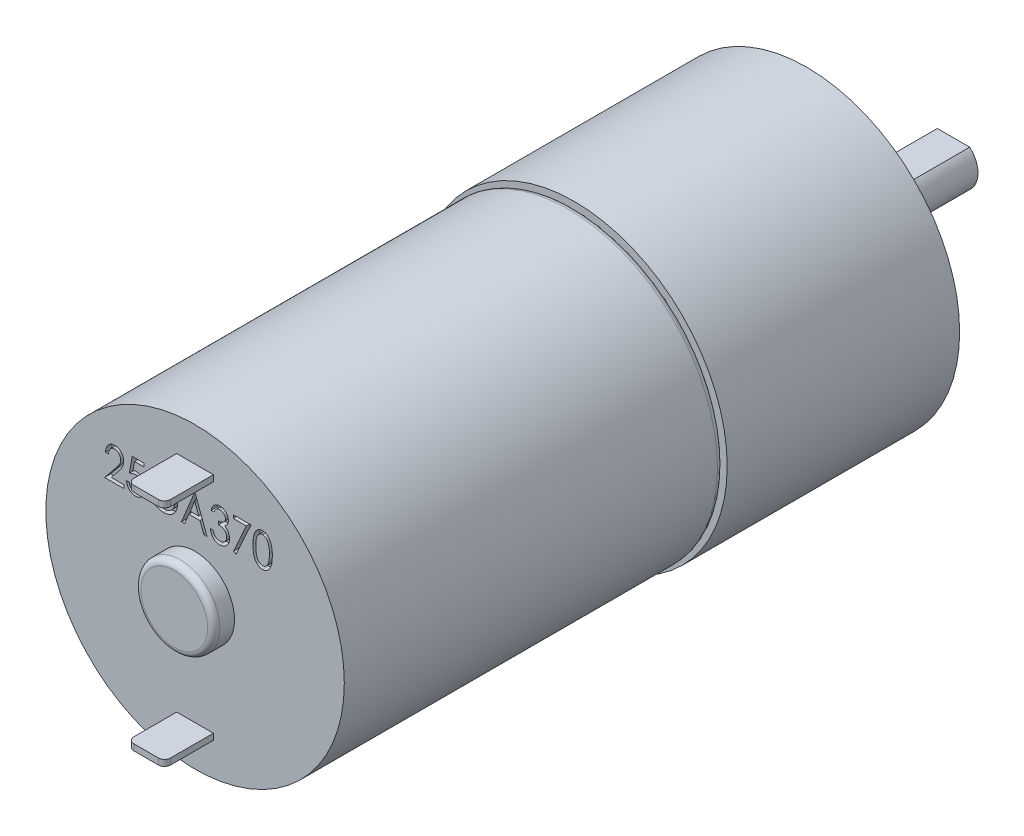
SolidWorks part; units mm, degrees
ref_plane "Front Plane" through (0, 0, 0) normal (0, 0, 1) x (1, 0, 0)
ref_plane "Top Plane" through (0, 0, 0) normal (0, 1, 0) x (1, 0, 0)
ref_plane "Right Plane" through (0, 0, 0) normal (1, 0, 0) x (0, 0, -1)
sketch "Sketch1" plane through (0, 0, 0) normal (0, 0, 1) x (1, 0, 0)
  circle A0 centre (0, 0) radius 12.2
  dimension "D1" = 24.4
extrude "Boss-Extrude1" add sketch "Sketch1" along normal blind 31
fillet "Fillet1" radius 0.5 1 edges at (12.2, 0, 0)
sketch "Sketch2" plane through (0, 0, 0) normal (0, 0, -1) x (-1, 0, 0)
  circle A0 centre (0, 0) radius 12.5
  dimension "D1" = 25
extrude "Boss-Extrude2" add sketch "Sketch2" along normal blind 19
sketch "Sketch4" plane through (0, 0, -19) normal (0, 0, -1) x (-1, 0, 0)
  circle A0 centre (0, 0) radius 3.5
  circle A1 centre (0, 0) radius 2.5
  dimension "D1" = 7
  dimension "D2" = 5
extrude "Boss-Extrude3" add sketch "Sketch4" along normal blind 2.5 contours A0
sketch "Sketch6" plane through (0, 0, -21.5) normal (0, 0, -1) x (-1, 0, 0)
  circle A0 centre (0, 0) radius 2
  dimension "D1" = 4
extrude "Boss-Extrude4" add sketch "Sketch6" along normal blind 9.5
sketch "Sketch7" plane through (0, 0, -31) normal (0, 0, -1) x (-1, 0, 0)
  line L0 (-1.3229, 1.5) -> (1.3229, 1.5)
  line L1 (0, 0) -> (0, 12.5) construction
  circle A0 centre (0, 0) radius 2 construction
  arc A1 (-1.3229, 1.5) -> (1.3229, 1.5) centre (0, 0) cw
  circle A3 centre (0, 0) radius 12.5 construction
  dimension "D1" = 1.5
extrude "Cut-Extrude1" cut sketch "Sketch7" against normal blind 8
fillet "Fillet2" radius 1 1 edges at (0, 1.5, -23)
sketch "Sketch9" plane through (0, 0, 31) normal (0, 0, 1) x (1, 0, 0)
  circle A0 centre (0, 0) radius 3.225
  dimension "D1" = 6.45
extrude "Boss-Extrude5" add sketch "Sketch9" along normal blind 1.7
fillet "Fillet3" radius 0.5 1 edges at (3.225, 0, 32.7)
sketch "Sketch10" plane through (0, 0, 31) normal (0, 0, 1) x (1, 0, 0)
  line L0 (0, 11.2262) -> (0, -11.0261) construction
  line L1 (0, 0) -> (-8.0308, 0) construction
  line L2 (-1.5, 9.4) -> (1.5, 9.4)
  line L3 (-1.5, 9.4) -> (-1.5, 8.9)
  line L4 (-1.5, 8.9) -> (1.5, 8.9)
  line L5 (1.5, 9.4) -> (1.5, 8.9)
  line L6 (1.5, -9.4) -> (1.5, -8.9)
  line L7 (-1.5, -8.9) -> (1.5, -8.9)
  line L8 (-1.5, -9.4) -> (-1.5, -8.9)
  line L9 (-1.5, -9.4) -> (1.5, -9.4)
  point P7 (0, 8.9)
  point P15 (0, 9.4)
  dimension "D1" = 3
  dimension "D2" = 0.5
  dimension "D3" = 8.9
  dimension "D4" = 1.5
extrude "Boss-Extrude6" add sketch "Sketch10" along normal blind 4
fillet "Fillet4" radius 0.5 4 edges at (1.5, -9.15, 35) (-1.5, -9.15, 35) (1.5, 9.15, 35) (-1.5, 9.15, 35)
hole_wizard "M3 螺纹孔的螺纹孔钻头1" positions "Sketch12" profile "Sketch13" hole size "M3" standard "DIN"
sketch "Sketch12" plane through (0, 0, -19) normal (0, 0, -1) x (-1, 0, 0)
  point P0 (0, 8.5)
  point P2 (0, -8.5)
  dimension "D1" = 17
  dimension "D2" = 8.5
sketch "Sketch13" plane through (0, 8.5, -19) normal (1, 0, 0) x (0, 1, 0)
  line L0 (0, 0) -> (0, 4.2511)
  line L1 (0, 4.2511) -> (1.25, 3.5)
  line L2 (1.25, 3.5) -> (1.25, 0)
  line L5 (1.25, 0) -> (0, 0)
  line L10 (0, 4.2511) -> (-1.25, 3.5) construction
  line L11 (0, -6.35) -> (0, 107.95) construction
  dimension "Hole Dia." = 2.5
  dimension "Hole Depth" = 3.5
  dimension "Drill Angle" = 118
fillet "Fillet5" radius 0.25 1 edges at (-3.5, 0, -21.5)
sketch "Sketch14" plane through (0, 0, 31) normal (0, 0, 1) x (1, 0, 0)
  text T0 "25GA370" font "Century Gothic" height in points 10
extrude "Cut-Extrude2" cut sketch "Sketch14" against normal blind 0.5
